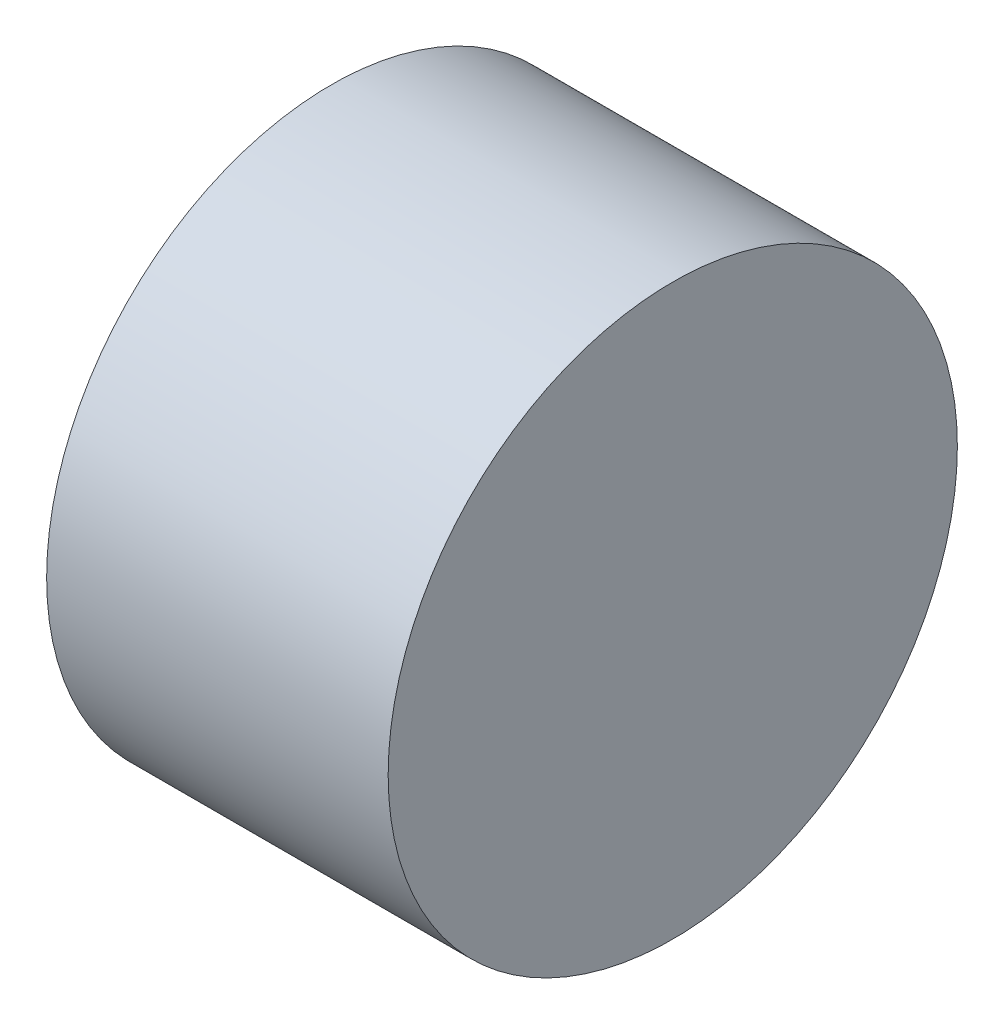
SolidWorks part; units mm, degrees
ref_plane "前视基准面" through (0, 0, 0) normal (0, 0, 1) x (1, 0, 0)
ref_plane "上视基准面" through (0, 0, 0) normal (0, 1, 0) x (1, 0, 0)
ref_plane "右视基准面" through (0, 0, 0) normal (1, 0, 0) x (0, 0, -1)
sketch "草图1" plane through (0, 0, 0) normal (1, 0, 0) x (0, 0, -1)
  circle A0 centre (0, 0) radius 50
  dimension "D1" = 100
extrude "凸台-拉伸1" add sketch "草图1" along normal blind 30 and the other way blind 30
ref_axis "基准轴1" through (-30, 0, 0) along (1, 0, 0)
